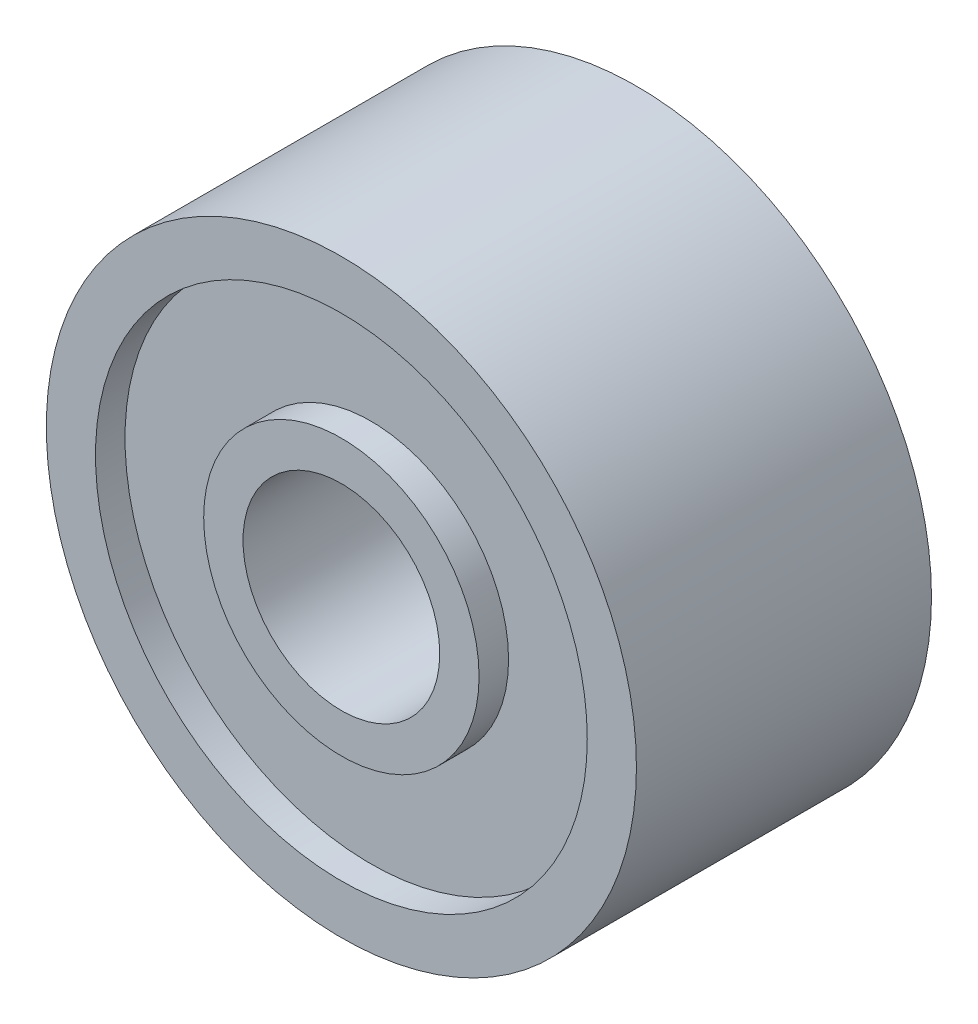
SolidWorks part; units mm, degrees
ref_plane "Front Plane" through (0, 0, 0) normal (0, 0, 1) x (1, 0, 0)
ref_plane "Top Plane" through (0, 0, 0) normal (0, 1, 0) x (1, 0, 0)
ref_plane "Right Plane" through (0, 0, 0) normal (1, 0, 0) x (0, 0, -1)
sketch "Sketch1" plane through (0, 0, 0) normal (0, 0, 1) x (1, 0, 0)
  circle A0 centre (0, 0) radius 1
  circle A1 centre (0, 0) radius 3
extrude "Boss-Extrude1" add sketch "Sketch1" along normal blind 3
sketch "Sketch2" plane through (0, 0, 3) normal (0, 0, 1) x (1, 0, 0)
  circle A0 centre (0, 0) radius 1.4
  circle A1 centre (0, 0) radius 2.5
extrude "Cut-Extrude1" cut sketch "Sketch2" against normal blind 0.3
extrude "Cut-Extrude2" cut sketch "Sketch2<2>" along normal blind 0.3 from surface starting at face at (3, 0, 0)
sketch "Sketch2<2>" plane through (0, 0, 3) normal (0, 0, 1) x (1, 0, 0) same geometry as "Sketch2"
